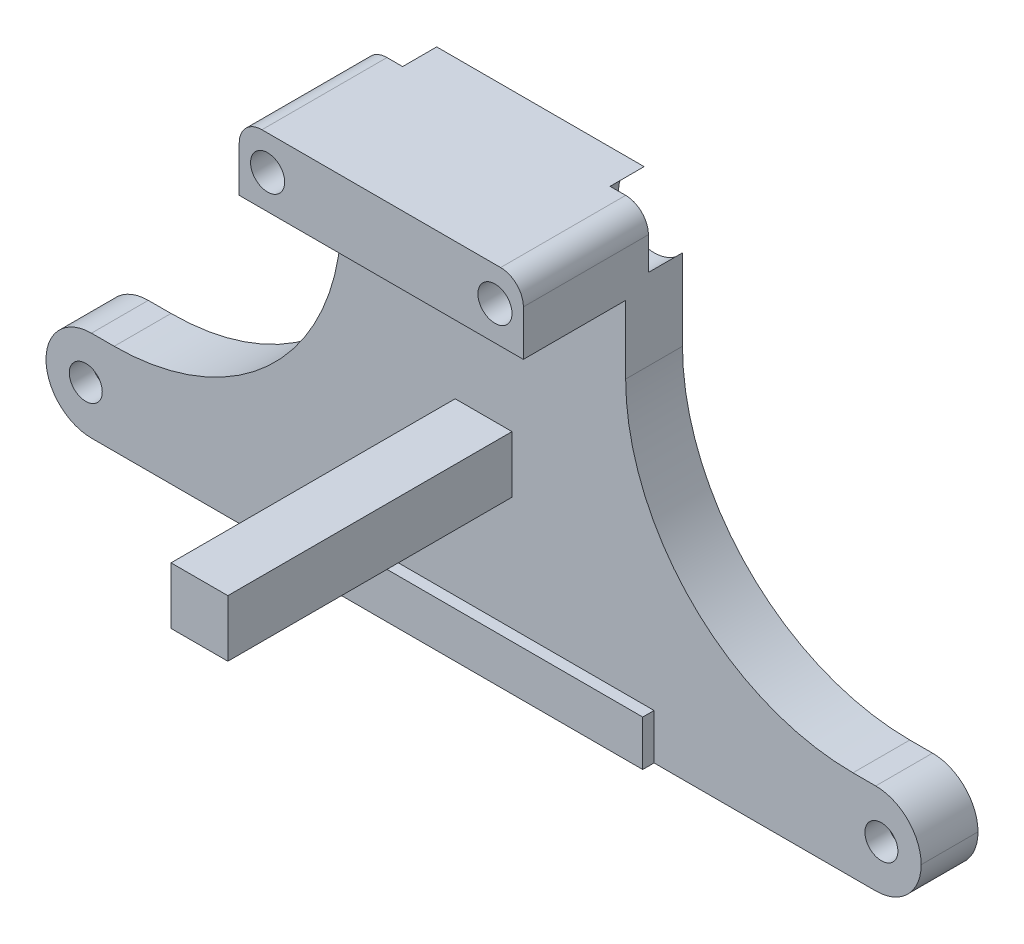
SolidWorks part; units mm, degrees
ref_plane "Спереди" through (0, 0, 0) normal (0, 0, 1) x (1, 0, 0)
ref_plane "Сверху" through (0, 0, 0) normal (0, 1, 0) x (1, 0, 0)
ref_plane "Справа" through (0, 0, 0) normal (1, 0, 0) x (0, 0, -1)
sketch "Эскиз1" plane through (0, 0, 0) normal (0, 0, 1) x (1, 0, 0)
  line L0 (-1000, 0) -> (49000, 0) construction
  line L1 (-38.5, -4) -> (38.5, -4)
  line L2 (-38.5, -4) -> (-38.5, 4)
  line L3 (-38.5, 4) -> (38.5, 4)
  line L4 (38.5, -4) -> (38.5, 4)
  line L5 (-38.5, -4) -> (38.5, 4) construction
  line L6 (-38.5, 4) -> (38.5, -4) construction
  circle A0 centre (-35, 0) radius 1.45
  circle A1 centre (35, 0) radius 1.45
  point P0 (0, 0)
  dimension "D2" = 2.9
  dimension "D1" = 8
  dimension "D3" = 70
  dimension "D4" = 35
  dimension "D5" = 77
extrude "Бобышка-Вытянуть1" add sketch "Эскиз1" along normal blind 5
sketch "Эскиз2" plane through (0, 0, 0) normal (0, 0, -1) x (-1, 0, 0)
  line L0 (-38.5, 4) -> (38.5, 4) construction
  line L1 (-12.5, 4) -> (12.5, 4)
  line L2 (-12.5, 4) -> (-12.5, 36)
  line L3 (-12.5, 36) -> (12.5, 36)
  line L4 (12.5, 4) -> (12.5, 36)
  line L5 (-12.5, 4) -> (12.5, 36) construction
  line L6 (-12.5, 36) -> (12.5, 4) construction
  line L7 (-1006.5256, 33) -> (48993.4744, 33) construction
  line L8 (0, -1000) -> (0, 49000) construction
  circle A0 centre (-10, 33) radius 1.5
  circle A1 centre (10, 33) radius 1.5
  point P4 (0, 20)
  dimension "D1" = 20
  dimension "D3" = 3
  dimension "D2" = 10
  dimension "D4" = 25
  dimension "D5" = 3
  dimension "D6" = 32
extrude "Бобышка-Вытянуть2" add sketch "Эскиз2" against normal blind 5
sketch "Эскиз3" plane through (0, 0, 5) normal (0, 0, -1) x (-1, 0, 0)
  line L0 (12.5, 4) -> (12.5, 36) construction
  line L1 (-12.5, 36) -> (12.5, 36)
  line L2 (-12.5, 36) -> (-12.5, 30)
  line L3 (-12.5, 30) -> (12.5, 30)
  line L4 (12.5, 36) -> (12.5, 30)
  line L5 (-12.5, 36) -> (12.5, 30) construction
  line L6 (-12.5, 30) -> (12.5, 36) construction
  circle A0 centre (10, 33) radius 1.5 construction
  circle A1 centre (-10, 33) radius 1.5 construction
  circle A2 centre (10, 33) radius 1.5
  circle A3 centre (-10, 33) radius 1.5
  point P4 (0, 33)
  dimension "D1" = 6
extrude "Бобышка-Вытянуть3" add sketch "Эскиз3" against normal blind 9
fillet "Скругление1" radius 20 2 edges at (12.5, 4, 2.5) (-12.5, 4, 2.5)
fillet "Скругление2" radius 4 4 edges at (-38.5, -4, 2.5) (-38.5, 4, 2.5) (38.5, -4, 2.5) (38.5, 4, 2.5)
fillet "Скругление3" radius 2 2 edges at (12.5, 36, 7) (-12.5, 36, 7)
sketch "Эскиз4" plane through (0, 0, 0) normal (0, 0, -1) x (-1, 0, 0)
  circle A0 centre (-10, 33) radius 3.125
  circle A1 centre (10, 33) radius 3.125
  circle A2 centre (-35, 0) radius 3.125
  circle A3 centre (35, 0) radius 3.125
  dimension "D1" = 6.25
extrude "Вырез-Вытянуть3" cut sketch "Эскиз4" against normal blind 3
sketch "Эскиз5" plane through (0, 0, 5) normal (0, 0, 1) x (1, 0, 0)
  line L0 (-34.5, -4) -> (34.5, -4) construction
  line L1 (15, -4) -> (-15, -4)
  line L2 (15, -4) -> (15, 0)
  line L3 (15, 0) -> (-15, 0)
  line L4 (-15, -4) -> (-15, 0)
  line L5 (15, -4) -> (-15, 0) construction
  line L6 (15, 0) -> (-15, -4) construction
  line L7 (12.5, 30) -> (12.5, 24) construction
  line L8 (-12.5, 24) -> (-12.5, 30) construction
  point P4 (0, -2)
  dimension "D1" = 2.5
  dimension "D2" = 2.5
  dimension "D3" = 4
extrude "Бобышка-Вытянуть4" add sketch "Эскиз5" along normal blind 1
sketch "Эскиз6" plane through (0, 0, 5) normal (0, 0, 1) x (1, 0, 0)
  line L0 (15, 0) -> (-15, 0) construction
  line L1 (-2.5, 15) -> (2.5, 15)
  line L2 (-2.5, 15) -> (-2.5, 10)
  line L3 (-2.5, 10) -> (2.5, 10)
  line L4 (2.5, 15) -> (2.5, 10)
  point P4 (0, 10)
  dimension "D1" = 5
  dimension "D2" = 5
  dimension "D3" = 10
extrude "Бобышка-Вытянуть5" add sketch "Эскиз6" along normal blind 25
